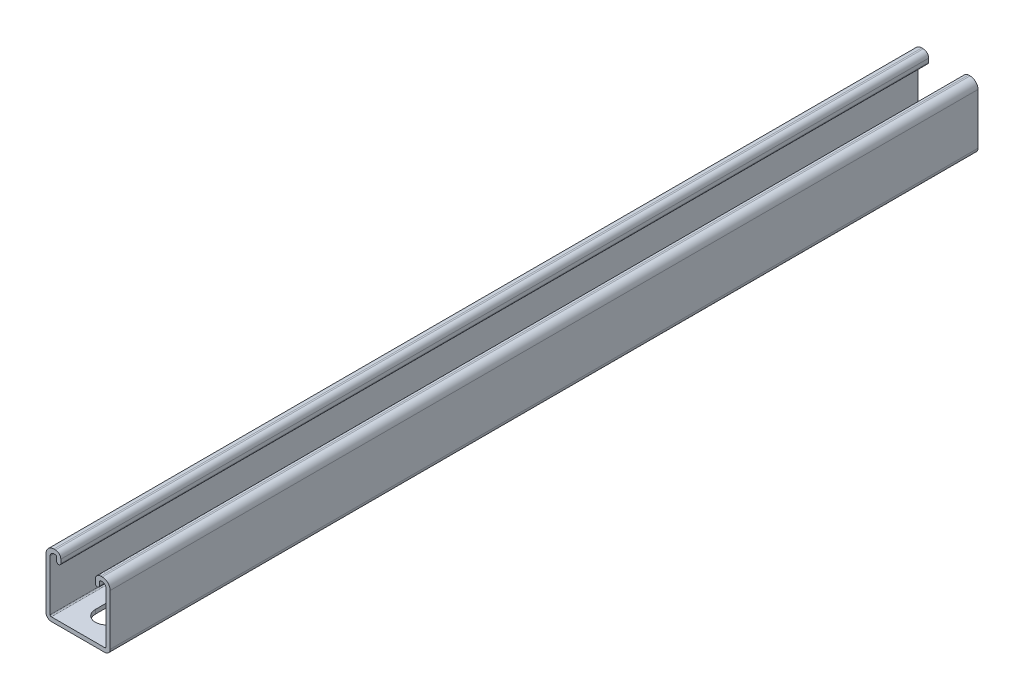
SolidWorks part; units mm, degrees
ref_plane "Front Plane" through (0, 0, 0) normal (0, 0, 1) x (1, 0, 0)
ref_plane "Top Plane" through (0, 0, 0) normal (0, 1, 0) x (1, 0, 0)
ref_plane "Right Plane" through (0, 0, 0) normal (1, 0, 0) x (0, 0, -1)
ref_plane "Plane1" through (0, 0, 3048) normal (0, 0, 1) x (1, 0, 0)
sketch "Sketch1" plane through (0, 0, 0) normal (0, 0, 1) x (1, 0, 0)
  line L0 (-20.6377, 0) -> (-17.9706, 0) construction
  line L1 (20.6377, 0) -> (17.9706, 0) construction
  line L2 (17.1769, -17.9704) -> (-17.1769, -17.9704)
  line L3 (-17.9706, -17.1766) -> (-17.9706, 15.5891)
  line L4 (-15.5894, 17.9704) -> (-14.5734, 17.9704)
  line L5 (-13.7797, 17.1766) -> (-13.7797, 14.8335)
  line L6 (-11.1127, 14.8335) -> (-11.1127, 17.1766)
  line L7 (-14.5734, 20.6374) -> (-15.5894, 20.6374)
  line L8 (-20.6377, 15.5891) -> (-20.6377, -17.1766)
  line L9 (-17.1769, -20.6374) -> (17.1769, -20.6374)
  line L10 (20.6377, 15.5891) -> (20.6377, -17.1766)
  line L11 (14.5734, 20.6374) -> (15.5894, 20.6374)
  line L12 (11.1127, 14.8335) -> (11.1127, 17.1766)
  line L13 (13.7797, 17.1766) -> (13.7797, 14.8335)
  line L14 (0, -17.9704) -> (0, -20.6374) construction
  line L15 (15.5894, 17.9704) -> (14.5734, 17.9704)
  line L16 (17.9706, -17.1766) -> (17.9706, 15.5891)
  arc A0 (-17.1769, -20.6374) -> (-20.6377, -17.1766) centre (-17.1769, -17.1766) cw
  arc A1 (-17.1769, -17.9704) -> (-17.9706, -17.1766) centre (-17.1769, -17.1766) cw
  arc A2 (-17.9706, 15.5891) -> (-15.5894, 17.9704) centre (-15.5894, 15.5891) cw
  arc A3 (-20.6377, 15.5891) -> (-15.5894, 20.6374) centre (-15.5894, 15.5891) cw
  arc A4 (-14.5734, 17.9704) -> (-13.7797, 17.1766) centre (-14.5734, 17.1766) cw
  arc A5 (-14.5734, 20.6374) -> (-11.1127, 17.1766) centre (-14.5734, 17.1766) cw
  arc A6 (-13.7797, 14.8335) -> (-11.1127, 14.8335) centre (-12.4462, 14.8335) ccw
  arc A7 (13.7797, 14.8335) -> (11.1127, 14.8335) centre (12.4462, 14.8335) cw
  arc A8 (14.5734, 20.6374) -> (11.1127, 17.1766) centre (14.5734, 17.1766) ccw
  arc A9 (14.5734, 17.9704) -> (13.7797, 17.1766) centre (14.5734, 17.1766) ccw
  arc A10 (20.6377, 15.5891) -> (15.5894, 20.6374) centre (15.5894, 15.5891) ccw
  arc A11 (17.9706, 15.5891) -> (15.5894, 17.9704) centre (15.5894, 15.5891) ccw
  arc A12 (17.1769, -17.9704) -> (17.9706, -17.1766) centre (17.1769, -17.1766) ccw
  arc A13 (17.1769, -20.6374) -> (20.6377, -17.1766) centre (17.1769, -17.1766) ccw
  dimension "D4" = 3.4608
  dimension "D5" = 5.0483
  dimension "D7" = 3.4608
  dimension "D1" = 34.3538
  dimension "D2" = 41.2748
  dimension "D3" = 2.667
  dimension "D6" = 1.016
  dimension "D8" = 2.3432
extrude "Primary Extrusion" add sketch "Sketch1" against normal blind 558.8
sketch "Sketch58" plane through (0, -20.6374, 0) normal (0, 1, 0) x (-1, 0, 0)
  line L0 (7.1438, -32.5438) -> (7.1438, -18.2562)
  line L1 (-7.1438, -18.2563) -> (-7.1438, -32.5438)
  line L2 (0, 22.7012) -> (0, -22.7012) construction
  line L3 (-7.1438, -25.4) -> (7.1438, -25.4) construction
  line L4 (17.1769, 0) -> (-17.1769, 0) construction
  arc A0 (7.1438, -32.5438) -> (-7.1438, -32.5438) centre (0, -32.5438) cw
  arc A1 (-7.1438, -18.2563) -> (7.1438, -18.2562) centre (0, -18.2563) cw
  dimension "D1" = 14.2875
  dimension "D2" = 14.2875
  dimension "D3" = 25.4
extrude "Slot Cut" cut sketch "Sketch58" along normal up to next contours L0 A1 L1 A0
pattern_linear "LPattern1" count 11 spacing 50.8 along (0, 0, -1) of "Slot Cut"
